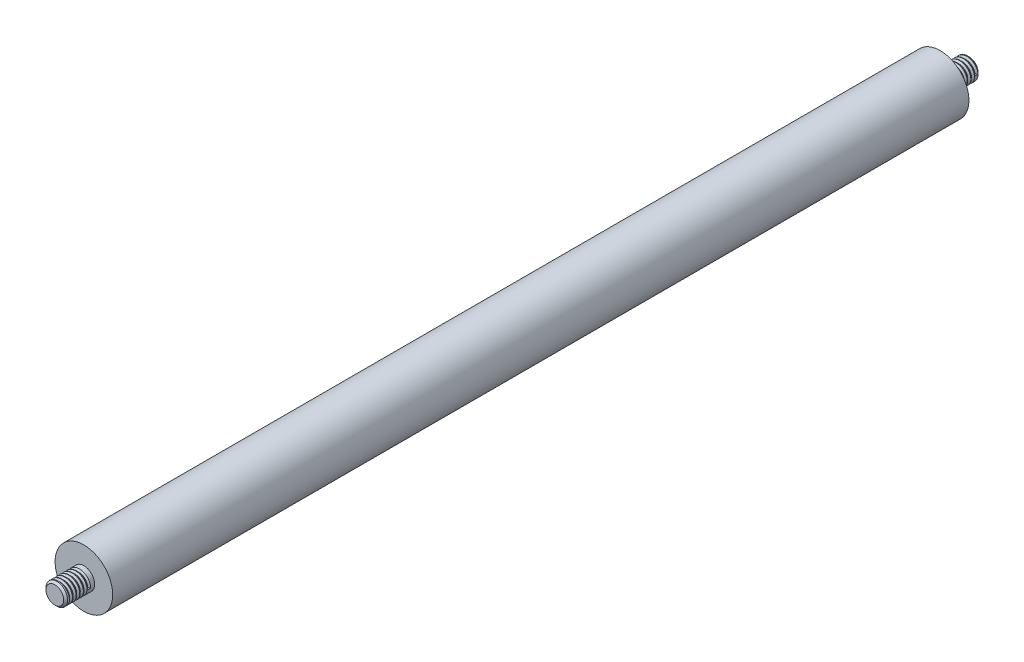
SolidWorks part; units mm, degrees
material "Cast Carbon Steel"
ref_plane "Front Plane" through (0, 0, 0) normal (0, 0, 1) x (1, 0, 0)
ref_plane "Top Plane" through (0, 0, 0) normal (0, 1, 0) x (1, 0, 0)
ref_plane "Right Plane" through (0, 0, 0) normal (1, 0, 0) x (0, 0, -1)
sketch "Sketch2" plane through (0, 0, 0) normal (0, 0, 1) x (1, 0, 0)
  circle A0 centre (0, 0) radius 12.7
  dimension "D1" = 25.4
extrude "Boss-Extrude1" add sketch "Sketch2" against normal blind 377.698
sketch "Sketch8" plane through (0, 0, 0) normal (1, 0, 0) x (0, 0, -1)
  line L0 (0, 0) -> (-12.8036, 0)
  line L1 (-12.8036, 0) -> (-12.8036, 3.9032)
  line L2 (-12.8036, 3.9032) -> (-11.9443, 4.7625)
  line L3 (0, 0) -> (0, 4.7625)
  line L5 (-11.9443, 4.7625) -> (0, 4.7625)
  dimension "D1" = 4.7625
  dimension "D2" = 3.9032
  dimension "D3" = 135
  dimension "D4" = 11.9443
revolve "Revolve1" add sketch "Sketch8" angle 360 about L0
thread "Thread2" pitch 1.5875 method cut profile "Thread Profile2" start angle 0, offset 0, length 8.763, pitch 1.5875, diameter 9.525
ref_plane "Plane2" through (-4.7625, 0, 11.9443) normal (0, -1, 0) x (-1, 0, 0)
sketch "Thread Profile2" plane through (-4.7625, 0, 11.9443) normal (0, -1, 0) x (-1, 0, 0)
  line L0 (0, 0) -> (0, 1.5875) construction
  line L11 (0, 0) -> (0, 1.3891)
  line L12 (0, 1.3891) -> (-0.8593, 0.893)
  line L13 (-0.8593, 0.893) -> (-0.8593, 0.4961)
  line L15 (-0.8593, 0.4961) -> (0, 0)
  line L17 (-0.8593, 0.6945) -> (0, 0.6945) construction
  point P2 (0, 0)
  dimension "Pitch" = 1.5875
  dimension "Profile_Angle" = 60
  dimension "Profile_Land" = 0.3969
  dimension "Profile_Height" = 0.8593
ref_plane "Plane3" through (0, 0, -188.849) normal (0, 0, 1) x (1, 0, 0)
mirror "Mirror3" about plane through (0, 0, -188.849) normal (0, 0, 1) of "Revolve1"
thread "Thread3" pitch 1.5875 method cut profile "Thread Profile3" start angle 0, offset 0, length 8.763, pitch 1.5875, diameter 9.525
ref_plane "Plane4" through (4.7625, 0, -389.6423) normal (0, -1, 0) x (1, 0, 0)
sketch "Thread Profile3" plane through (4.7625, 0, -389.6423) normal (0, -1, 0) x (1, 0, 0)
  line L0 (0, 0) -> (0, 1.5875) construction
  line L11 (0, 0) -> (0, 1.3891)
  line L12 (0, 1.3891) -> (-0.8593, 0.893)
  line L13 (-0.8593, 0.893) -> (-0.8593, 0.4961)
  line L15 (-0.8593, 0.4961) -> (0, 0)
  line L17 (-0.8593, 0.6945) -> (0, 0.6945) construction
  point P2 (0, 0)
  dimension "Pitch" = 1.5875
  dimension "Profile_Angle" = 60
  dimension "Profile_Land" = 0.3969
  dimension "Profile_Height" = 0.8593
